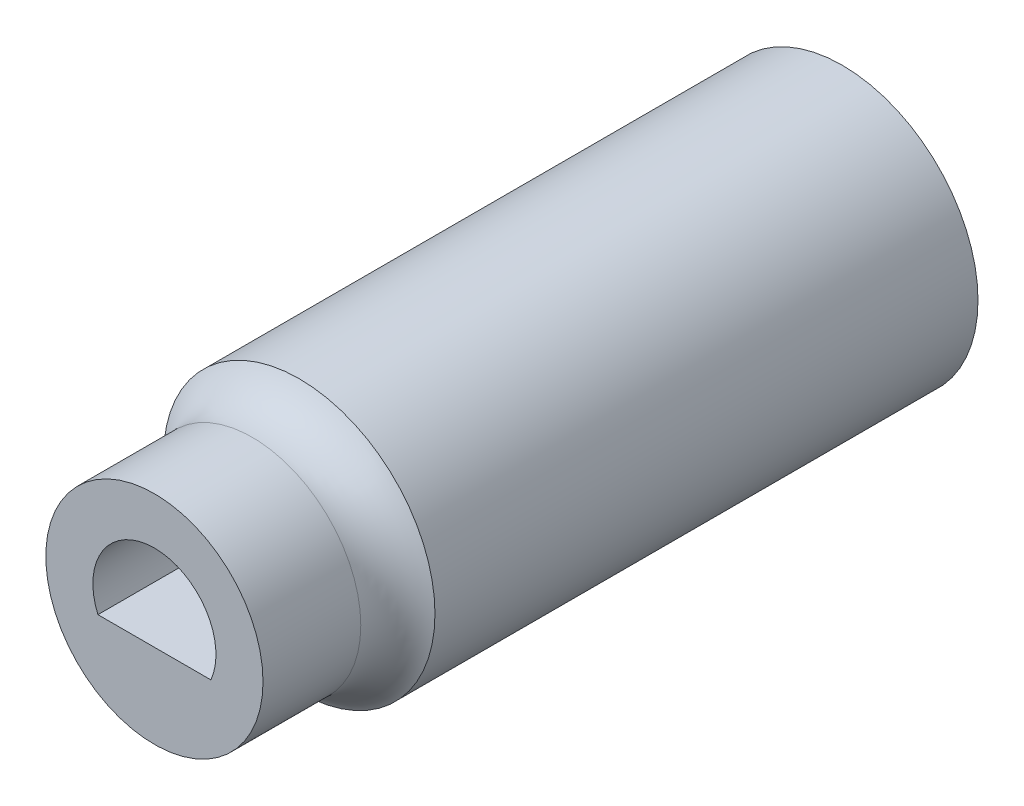
SolidWorks part; units mm, degrees
ref_plane "Ön Düzlem" through (0, 0, 0) normal (0, 0, 1) x (1, 0, 0)
ref_plane "Üst Düzlem" through (0, 0, 0) normal (0, 1, 0) x (1, 0, 0)
ref_plane "Sağ Düzlem" through (0, 0, 0) normal (1, 0, 0) x (0, 0, -1)
sketch "Çizim1" plane through (0, 0, 0) normal (0, 0, 1) x (1, 0, 0)
  circle A0 centre (0, 0) radius 7.5
extrude "Yükseklik-Ekstrüzyon1" add sketch "Çizim1" along normal blind 38
sketch "Çizim2" plane through (0, 0, 38) normal (0, 0, 1) x (1, 0, 0)
  line L1 (0, -1.35) -> (-2.735, -1.35)
  line L2 (0, -1.35) -> (2.735, -1.35)
  arc A0 (2.735, -1.35) -> (-2.735, -1.35) centre (0, 0) ccw
extrude "Kes-Ekstrüzyon1" cut sketch "Çizim2" against normal blind 9.5
sketch "Çizim3" plane through (0, 0, 0) normal (0, 0, -1) x (-1, 0, 0)
  line L1 (0, -2.05) -> (-3.2588, -2.05)
  line L2 (0, -2.05) -> (3.2588, -2.05)
  arc A1 (3.2588, -2.05) -> (-3.2588, -2.05) centre (0, 0) ccw
extrude "Kes-Ekstrüzyon3" cut sketch "Çizim3" against normal blind 25
sketch "Çizim4" plane through (0, 0, 38) normal (0, 0, 1) x (1, 0, 0)
  circle A0 centre (0, 0) radius 6
  circle A1 centre (0, 0) radius 7.5
extrude "Kes-Ekstrüzyon4" cut sketch "Çizim4" against normal blind 8
fillet "Radyus1" radius 3 1 edges at (6, 0, 30)
sketch "Çizim5" plane through (0, 0, 38) normal (0, 0, 1) x (1, 0, 0)
  line L0 (-3.1205, -1.35) -> (3.1205, -1.35)
  arc A0 (3.1205, -1.35) -> (-3.1205, -1.35) centre (0, 0) ccw
extrude "Kes-Ekstrüzyon5" cut sketch "Çizim5" against normal blind 10
sketch "Çizim6" plane through (0, 0, 0) normal (0, 0, -1) x (-1, 0, 0)
  line L0 (-3.4347, -2.05) -> (3.4347, -2.05)
  arc A0 (3.4347, -2.05) -> (-3.4347, -2.05) centre (0, 0) ccw
extrude "Kes-Ekstrüzyon6" cut sketch "Çizim6" against normal blind 25
sketch "Çizim8" plane through (0, 0, 0) normal (0, 0, -1) x (-1, 0, 0)
  line L0 (-3.8933, -2.05) -> (3.8933, -2.05)
  arc A0 (3.8933, -2.05) -> (-3.8933, -2.05) centre (0, 0) ccw
extrude "Kes-Ekstrüzyon7" cut sketch "Çizim8" against normal blind 25
